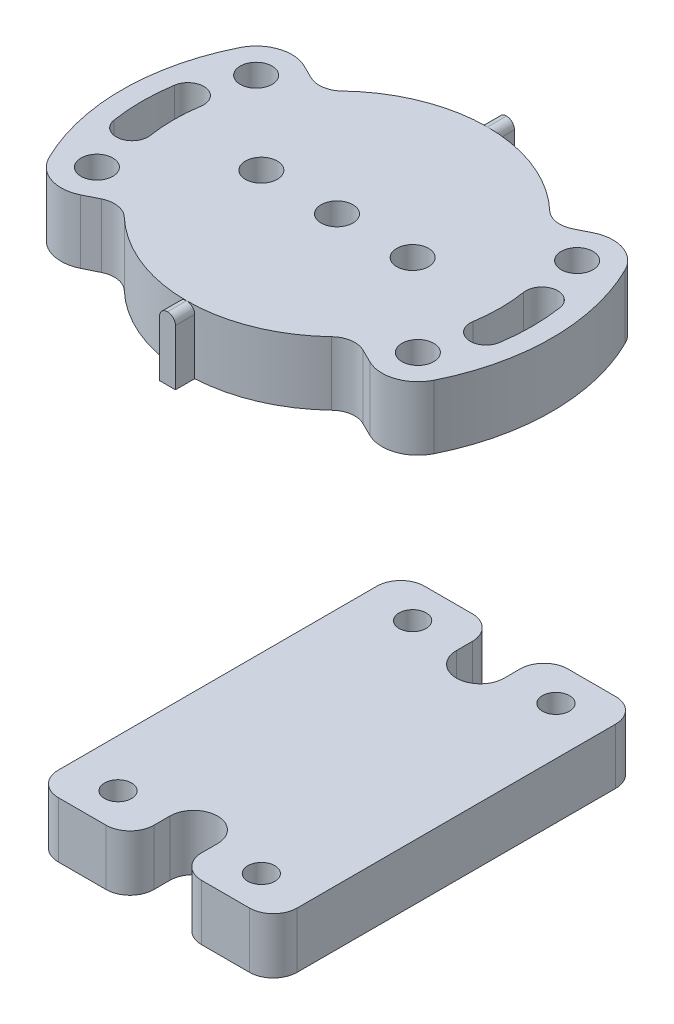
SolidWorks part; units mm, degrees
ref_plane "Front Plane" through (0, 0, 0) normal (0, 0, 1) x (1, 0, 0)
ref_plane "Top Plane" through (0, 0, 0) normal (0, 1, 0) x (1, 0, 0)
ref_plane "Right Plane" through (0, 0, 0) normal (1, 0, 0) x (0, 0, -1)
sketch "Sketch1" plane through (0, 0, 0) normal (0, 1, 0) x (1, 0, 0)
  line L0 (0, 0) -> (0, 13.7141) construction
  line L1 (5.0402, 0.9249) -> (5.0402, 0.9716)
  line L2 (0, 0) -> (0, 18.1232) construction
  line L3 (0, 0) -> (49.6134, 0) construction
  line L5 (1, -21.2869) -> (1, -18.2869)
  line L6 (18.1556, 14.0311) -> (14.4438, 12.1896)
  line L7 (22.1556, 5.9689) -> (18.4438, 4.1273)
  line L8 (20.1556, 10) -> (0, 0) construction
  line L9 (22.1556, -5.9689) -> (18.4438, -4.1273)
  line L10 (18.1556, -14.0311) -> (14.4438, -12.1896)
  line L11 (-18.1556, -14.0311) -> (-14.4438, -12.1896)
  line L12 (-22.1556, -5.9689) -> (-18.4438, -4.1273)
  line L13 (-22.1556, 5.9689) -> (-18.4438, 4.1273)
  line L14 (-18.1556, 14.0311) -> (-14.4438, 12.1896)
  line L15 (-1, 21.2869) -> (1, 21.2869)
  line L16 (-1, 21.2869) -> (-1, 18.2869)
  line L17 (-1, 18.2869) -> (1, 18.2869)
  line L18 (1, 21.2869) -> (1, 18.2869)
  line L19 (-1, -18.2869) -> (1, -18.2869)
  line L20 (-1, -21.2869) -> (-1, -18.2869)
  line L21 (-1, -21.2869) -> (1, -21.2869)
  arc A0 (-24.1868, 12) -> (-24.1868, -12) centre (0, 0) ccw
  circle A1 centre (0, 0) radius 2
  circle A4 centre (-9.5, 0) radius 2
  circle A5 centre (9.5, 0) radius 2
  circle A6 centre (-20.1556, 10) radius 2
  circle A7 centre (20.1556, 10) radius 2
  circle A8 centre (20.1556, -10) radius 2
  circle A9 centre (-20.1556, -10) radius 2
  circle A10 centre (0, 0) radius 22.5 construction
  circle A11 centre (0, 0) radius 18.9
  arc A12 (21.7425, 5.7891) -> (17.7626, 13.8109) centre (20.1556, 10) ccw
  arc A13 (21.7425, -5.7891) -> (17.7626, -13.8109) centre (20.1556, -10) cw
  arc A14 (-21.7425, -5.7891) -> (-17.7626, -13.8109) centre (-20.1556, -10) ccw
  arc A15 (-21.7425, 5.7891) -> (-17.7626, 13.8109) centre (-20.1556, 10) cw
  circle A17 centre (22.2261, 3.5) radius 2
  circle A18 centre (22.2261, -3.5) radius 2
  arc A19 (20.2505, 3.1889) -> (20.2505, -3.1889) centre (0, 0) cw
  arc A20 (24.2018, 3.8111) -> (24.2018, -3.8111) centre (0, 0) cw
  arc A21 (24.1868, -12) -> (24.1868, 12) centre (0, 0) ccw
  circle A23 centre (-22.2261, -3.5) radius 2
  arc A24 (-20.2505, 3.1889) -> (-20.2505, -3.1889) centre (0, 0) ccw
  arc A25 (-24.2018, 3.8111) -> (-24.2018, -3.8111) centre (0, 0) ccw
  circle A26 centre (-22.2261, 3.5) radius 2
  dimension "D2" = 4
  dimension "D4" = 4
  dimension "D5" = 4
  dimension "D7" = 45
  dimension "D9" = 9
  dimension "D10" = 37.8
  dimension "D11" = 4
  dimension "D3" = 19
  dimension "D6" = 20
  dimension "D8" = 2
  dimension "D12" = 7
  dimension "D13" = 3
extrude "Boss-Extrude1" add sketch "Sketch1" against normal blind 8 contours A0 A7 A6 A5 A4 A1 A8 A9 | A13 L9 A11 L10 A8 | L7 A12 L6 A11 A7 | A15 L13 A11 L14 A6 | L12 A14 L11 A11 A9 | L9 A13 A0 A12 L7 A11 A17 A20 A18 A19 | A11 L18 L15 L16 | L18 A11 L16 L17 | A11 L20 L21 L5 | L13 A15 A0 A14 L12 A11 A25 A26 A24 A23 | L20 A11 L5 L19 region at (0, 0, 20.089) region at (0, 0, 18.5891) region at (1.5342, 0, 18.5802) region at (17.0611, 0, 8.4647) region at (-16.3644, 0, 12.98) region at (19.0389, 0, 2.1042) region at (-20.413, 0, 4.8198) region at (-20.2351, 0, -5.1785) region at (24.2824, 0, -8.6102) region at (0, 0, -18.5891) region at (0, 0, -20.089)
ref_plane "Plane1" through (0, -58, 0) normal (0, -1, 0) x (-1, 0, 0)
sketch "Sketch4" plane through (0, -58, 0) normal (0, -1, 0) x (-1, 0, 0)
  line L0 (-1000, 0) -> (49000, 0) construction
  line L1 (-12, 23) -> (-6, 23)
  line L2 (-15, 20) -> (-15, -20)
  line L3 (-12, -23) -> (-6, -23)
  line L4 (15, 20) -> (15, -20)
  line L5 (0, -1000) -> (0, 49000) construction
  line L8 (-3, 20) -> (-3, 18)
  line L10 (3, 20) -> (3, 18)
  line L11 (3, -20) -> (3, -18)
  line L13 (-3, -20) -> (-3, -18)
  line L14 (6, 23) -> (12, 23)
  line L15 (6, -23) -> (12, -23)
  circle A0 centre (-9, 18.5) radius 1.7
  circle A2 centre (9, 18.5) radius 1.7
  circle A3 centre (9, -18.5) radius 1.7
  circle A4 centre (-9, -18.5) radius 1.7
  arc A5 (12, -23) -> (15, -20) centre (12, -20) ccw
  arc A6 (6, -23) -> (3, -20) centre (6, -20) cw
  arc A7 (-3, -20) -> (-6, -23) centre (-6, -20) cw
  arc A8 (-12, -23) -> (-15, -20) centre (-12, -20) cw
  arc A9 (15, 20) -> (12, 23) centre (12, 20) ccw
  arc A10 (6, 23) -> (3, 20) centre (6, 20) ccw
  arc A11 (-3, 20) -> (-6, 23) centre (-6, 20) ccw
  arc A12 (-15, 20) -> (-12, 23) centre (-12, 20) cw
  arc A13 (-3, 18) -> (3, 18) centre (0, 18) ccw
  arc A14 (3, -18) -> (-3, -18) centre (0, -18) ccw
  point P29 (3, -23)
  point P32 (-3, -23)
  point P39 (3, 23)
  point P42 (-3, 23)
  dimension "D3" = 3.4
  dimension "D7" = 3
  dimension "D9" = 3
  dimension "D10" = 3
  dimension "D1" = 18
  dimension "D2" = 37
  dimension "D4" = 6
  dimension "D5" = 4.5
  dimension "D6" = 6
  dimension "D8" = 5
extrude "Boss-Extrude3" add sketch "Sketch4" along normal blind 7 separate body
fillet "Fillet2" radius 3 4 edges at (-14.4438, -4, 12.1896) (14.4438, -4, 12.1896) (-14.4438, -4, -12.1896) (14.4438, -4, -12.1896)
fillet "Fillet3" radius 1 4 edges at (-1, 0, -20.0802) (1, 0, -20.0802) (-1, 0, 20.0802) (1, 0, 20.0802)
